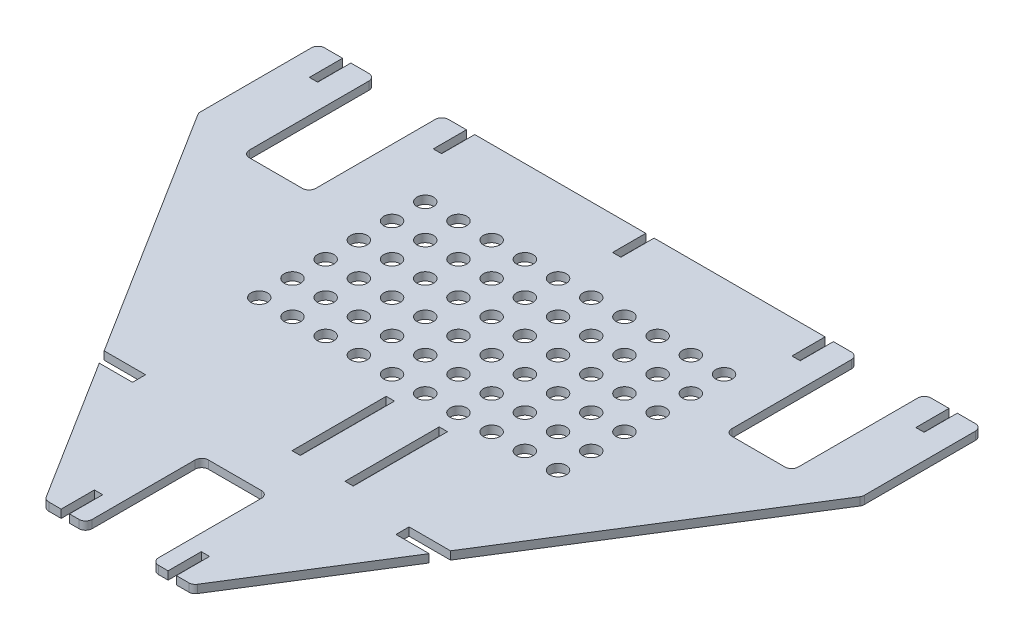
SolidWorks part; units mm, degrees
material "Corrugated Paper"
ref_plane "Front Plane" through (0, 0, 0) normal (0, 0, 1) x (1, 0, 0)
ref_plane "Top Plane" through (0, 0, 0) normal (0, 1, 0) x (1, 0, 0)
ref_plane "Right Plane" through (0, 0, 0) normal (1, 0, 0) x (0, 0, -1)
sketch "Sketch1" plane through (0, 0, 0) normal (0, 1, 0) x (1, 0, 0)
  line L0 (0, 0) -> (0, -142.875) construction
  line L1 (12.7, -57.15) -> (-12.7, -57.15)
  line L2 (-12.7, -57.15) -> (-12.7, -101.6)
  line L3 (-12.7, -101.6) -> (-18.8595, -101.6)
  line L4 (-28.194, -101.6) -> (-127, 55.88)
  line L5 (-127, 55.88) -> (-127, 101.6)
  line L6 (-127, 101.6) -> (-117.5893, 101.6)
  line L7 (-105.0036, 101.6) -> (-105.0036, 50.8)
  line L9 (-105.0036, 50.8) -> (-79.6036, 50.8)
  line L10 (-79.6036, 50.8) -> (-79.6036, 101.6)
  line L11 (-79.6036, 101.6) -> (-70.1929, 101.6)
  line L13 (79.6036, 50.8) -> (79.6036, 101.6)
  line L14 (105.0036, 50.8) -> (79.6036, 50.8)
  line L15 (105.0036, 101.6) -> (105.0036, 50.8)
  line L16 (127, 101.6) -> (117.5893, 101.6)
  line L17 (127, 55.88) -> (127, 101.6)
  line L18 (28.194, -101.6) -> (127, 55.88)
  line L19 (12.7, -101.6) -> (18.8595, -101.6)
  line L20 (12.7, -57.15) -> (12.7, -101.6)
  line L21 (-127, 101.6) -> (127, -101.6) construction
  line L22 (-22.0345, -101.6) -> (-28.194, -101.6)
  line L24 (-22.0345, -101.6) -> (-22.0345, -88.9)
  line L25 (-22.0345, -88.9) -> (-18.8595, -88.9)
  line L26 (-18.8595, -101.6) -> (-18.8595, -88.9)
  line L27 (22.0345, -101.6) -> (22.0345, -88.9)
  line L28 (22.0345, -88.9) -> (18.8595, -88.9)
  line L29 (18.8595, -101.6) -> (18.8595, -88.9)
  line L30 (22.0345, -101.6) -> (28.194, -101.6)
  line L31 (-92.3036, 50.8) -> (-92.3036, 101.6) construction
  line L32 (-114.4143, 101.6) -> (-105.0036, 101.6)
  line L34 (-117.5893, 101.6) -> (-117.5893, 88.9)
  line L35 (-117.5893, 88.9) -> (-114.4143, 88.9)
  line L36 (-114.4143, 101.6) -> (-114.4143, 88.9)
  line L37 (-67.0179, 101.6) -> (-67.0179, 88.9)
  line L38 (-67.0179, 88.9) -> (-70.1929, 88.9)
  line L39 (-70.1929, 101.6) -> (-70.1929, 88.9)
  line L40 (-67.0179, 101.6) -> (67.0179, 101.6)
  line L41 (117.5893, 101.6) -> (117.5893, 88.9)
  line L42 (117.5893, 88.9) -> (114.4143, 88.9)
  line L43 (114.4143, 101.6) -> (114.4143, 88.9)
  line L44 (67.0179, 101.6) -> (67.0179, 88.9)
  line L45 (70.1929, 101.6) -> (70.1929, 88.9)
  line L46 (67.0179, 88.9) -> (70.1929, 88.9)
  line L47 (70.1929, 101.6) -> (79.6036, 101.6)
  line L48 (114.4143, 101.6) -> (105.0036, 101.6)
  point P26 (0, -57.15)
  dimension "D2" = 25.4
  dimension "D3" = 254
  dimension "D5" = 44.45
  dimension "D6" = 50.8
  dimension "D7" = 203.2
  dimension "D8" = 45.72
  dimension "D9" = 21.9964
  dimension "D4" = 15.494
  dimension "D10" = 3.175
  dimension "D11" = 12.7
  dimension "D12" = 3.175
extrude "Boss-Extrude1" add sketch "Sketch1" along normal blind 3.0988 contours L13 L47 L45 L46 L44 L40 L37 L38 L39 L11 L10 L9 L7 L32 L36 L35 L34 L6 L5 L4 L22 L24 L25 L26 L3 L2 L1 L20 L19 L29 L28 L27 L30 L18 L17 L16 L41 L42 L43 L48 L15 L14
sketch "Sketch2" plane through (0, 3.0988, 0) normal (0, 1, 0) x (1, 0, 0)
  line L0 (14.4907, 0) -> (14.4907, 54.8341) construction
  line L6 (-67.0179, 88.9) -> (-70.1929, 88.9) construction
  line L7 (2.7686, -2.0574) -> (5.9436, -2.0574)
  line L8 (2.7686, -2.0574) -> (2.7686, -38.1)
  line L9 (2.7686, -38.1) -> (5.9436, -38.1)
  line L10 (5.9436, -2.0574) -> (5.9436, -38.1)
  line L11 (-22.0345, -101.6) -> (-28.2321, -101.6)
  line L12 (23.0378, -2.0574) -> (23.0378, -38.1)
  line L13 (26.2128, -38.1) -> (23.0378, -38.1)
  line L14 (26.2128, -2.0574) -> (26.2128, -38.1)
  line L15 (26.2128, -2.0574) -> (23.0378, -2.0574)
  line L16 (-22.0345, -101.6) -> (-22.0345, -69.85)
  line L17 (12.7, -57.15) -> (-12.7, -57.15) construction
  line L18 (-22.0345, -69.85) -> (-28.2321, -69.85)
  line L19 (-28.2321, -101.6) -> (-28.2321, -69.85)
  line L20 (-18.8595, -101.6) -> (-18.8595, -88.9) construction
  line L21 (0, -69.85) -> (0, -120.65) construction
  line L22 (1.5494, -69.85) -> (-1.5494, -69.85) construction
  line L23 (1.5494, -69.85) -> (1.5494, -120.65) construction
  line L24 (1.5494, -120.65) -> (-1.5494, -120.65) construction
  line L25 (-1.5494, -69.85) -> (-1.5494, -120.65) construction
  line L26 (-18.8595, -95.25) -> (-1.5494, -95.25) construction
  line L27 (1.5494, -95.25) -> (18.8595, -95.25) construction
  line L28 (18.8595, -101.6) -> (18.8595, -88.9) construction
  line L29 (-1.5494, -84.7475) -> (-7.747, -84.7475) construction
  line L30 (-1.5494, -84.7475) -> (-1.5494, -105.7525) construction
  line L31 (-1.5494, -105.7525) -> (-7.747, -105.7525) construction
  line L32 (-7.747, -84.7475) -> (-7.747, -105.7525) construction
  dimension "D3" = 23.4442
  dimension "D1" = 36.0426
  dimension "D2" = 19.05
  dimension "D5" = 6.1976
  dimension "D6" = 31.75
  dimension "D8" = 3.0988
  dimension "D9" = 50.8
  dimension "D4" = 6.1976
  dimension "D7" = 4.318
extrude "Cut-Extrude1" cut sketch "Sketch2" against normal through all contours L10 L9 L8 L7 | L12 L13 L14 L15
fillet "Fillet1" radius 2.54 18 edges at (105.0036, 1.5494, -50.8) (105.0036, 1.5494, -101.6) (12.7, 1.5494, 101.6) (12.7, 1.5494, 57.15) (-12.7, 1.5494, 57.15) (-12.7, 1.5494, 101.6) (-127, 1.5494, -55.88) (-127, 1.5494, -101.6) (-105.0036, 1.5494, -101.6) (-105.0036, 1.5494, -50.8) (-79.6036, 1.5494, -50.8) (-79.6036, 1.5494, -101.6) (79.6036, 1.5494, -101.6) (79.6036, 1.5494, -50.8) (127, 1.5494, -101.6) (127, 1.5494, -55.88) (28.194, 1.5494, 101.6) (-28.194, 1.5494, 101.6)
sketch "Sketch3" plane through (0, 3.0988, 0) normal (0, 1, 0) x (1, 0, 0)
  line L0 (-79.6036, 53.34) -> (-79.6036, 99.06) construction
  line L1 (-67.0179, 88.9) -> (-70.1929, 88.9) construction
  circle A0 centre (-54.2036, 69.85) radius 3.175
  dimension "D1" = 6.35
  dimension "D2" = 25.4
  dimension "D3" = 19.05
extrude "Cut-Extrude2" cut sketch "Sketch3" against normal through all
pattern_linear "LPattern1" count 10 spacing 12.7 along (1, 0, 0) count 6 spacing 12.7 along (0, 0, 1) of "Cut-Extrude2"
sketch "Sketch4" plane through (0, 3.0988, 0) normal (0, 1, 0) x (1, 0, 0)
  line L0 (0, -164.31) -> (0, 101.6) construction
  line L1 (-63.105, 101.6) -> (63.105, 101.6) construction
  line L2 (-63.105, 101.6) -> (-63.105, -164.31) construction
  line L3 (-63.105, -164.31) -> (63.105, -164.31) construction
  line L4 (63.105, 101.6) -> (63.105, -164.31) construction
  line L5 (28.9407, -100.4099) -> (126.6116, 55.2609) construction
  line L6 (66.2524, -40.9413) -> (50.405, -40.9413)
  line L7 (66.2524, -40.9413) -> (66.2524, -45.9578)
  line L8 (66.2524, -45.9578) -> (50.405, -45.9578)
  line L9 (50.405, -40.9413) -> (50.405, -45.9578)
  line L10 (-50.405, -40.9413) -> (-50.405, -45.9578)
  line L11 (-66.2524, -45.9578) -> (-50.405, -45.9578)
  line L12 (-66.2524, -40.9413) -> (-66.2524, -45.9578)
  line L13 (-66.2524, -40.9413) -> (-50.405, -40.9413)
  line L14 (-67.0179, 101.6) -> (67.0179, 101.6) construction
  line L15 (-1.5875, 101.6) -> (1.5875, 101.6)
  line L16 (-1.5875, 101.6) -> (-1.5875, 88.9)
  line L17 (-1.5875, 88.9) -> (1.5875, 88.9)
  line L18 (1.5875, 101.6) -> (1.5875, 88.9)
  point P8 (63.105, -45.9578)
  point P11 (0, 101.6)
  dimension "D1" = 265.91
  dimension "D2" = 126.21
  dimension "D5" = 3.175
  dimension "D6" = 12.7
  dimension "D4" = 12.7
  dimension "D3" = 5.0165
extrude "Cut-Extrude3" cut sketch "Sketch4" against normal through all
equation "\"D1@Boss-Extrude1\" = \"thick\""
equation "\"D4@Sketch1\"=\"thick\" * 5"
equation "\"D10@Sketch1\"=\"thick\"+\"clear\""
equation "\"D9@Sketch1\" = \"thick\" * 3 + 0.5"
equation "\"D12@Sketch1\"=\"thick\"+\"clear\""
equation "\"D3@Sketch2\"=\"MotorLength@Motor-1.Part\""
equation "\"D1@Sketch2\" =  ( \"MotorDiameter@Motor-1.Part\" + 0.5 ) "
equation "\"rodThick\"= 0.085in"
equation "\"thick\"= 0.122in"
equation "\"D5@Sketch2\"=2*\"thick\""
equation "\"clear\"= 0.003in"
equation "\"D5@Sketch4\"=\"thick\"+\"clear\""
equation "\"D8@Sketch2\"=\"thick\""
equation "\"D4@Sketch2\"=2*\"thick\""
